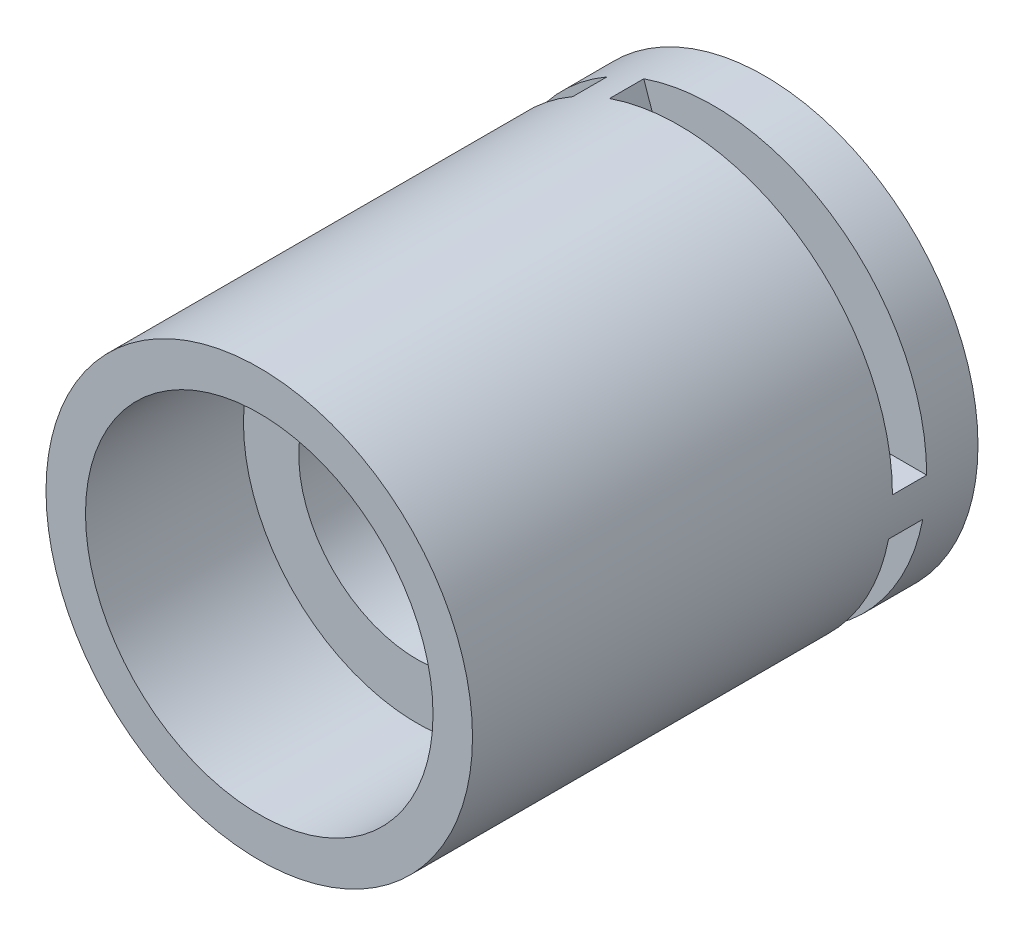
SolidWorks part; units mm, degrees
ref_plane "Front Plane" through (0, 0, 0) normal (0, 0, 1) x (1, 0, 0)
ref_plane "Top Plane" through (0, 0, 0) normal (0, 1, 0) x (1, 0, 0)
ref_plane "Right Plane" through (0, 0, 0) normal (1, 0, 0) x (0, 0, -1)
sketch "Sketch2" plane through (0, 0, 0) normal (0, 0, 1) x (1, 0, 0)
  circle A0 centre (0, 0) radius 13.5
  dimension "D1" = 27
extrude "Boss-Extrude1" add sketch "Sketch2" against normal blind 32
ref_plane "Plane1" through (0, 0, 0) normal (0, 0, 1) x (1, 0, 0)
sketch "Sketch4" plane through (0, 0, 0) normal (0, 0, 1) x (1, 0, 0)
  circle A0 centre (0, 0) radius 11
  dimension "D1" = 22
extrude "Cut-Extrude1" cut sketch "Sketch4" against normal blind 10
sketch "Sketch5" plane through (0, 0, 0) normal (0, 0, 1) x (1, 0, 0)
  circle A0 centre (0, 0) radius 7.5
  dimension "D1" = 15
extrude "Cut-Extrude2" cut sketch "Sketch5" against normal blind 30
sketch "Sketch9" plane through (0, 0, -32) normal (0, 0, -1) x (-1, 0, 0)
  line L0 (0, -18.8285) -> (0, 25.3406) construction
sketch3d "3DSketch4"
  point P0 (4.7437, 12.6391, -18.7172)
ref_plane "Plane5" through (0, 13.5, 0) normal (0, 1, 0) x (1, 0, 0)
sketch "Sketch10" plane through (0, 13.5, 0) normal (0, 1, 0) x (1, 0, 0)
  line L0 (13.5, 32) -> (-13.5, 32) construction
  line L1 (-4.4913, 28.75) -> (21.2187, 28.75)
  line L2 (-4.4913, 28.75) -> (-4.4913, 26.584)
  line L3 (-4.4913, 26.584) -> (21.2187, 26.584)
  line L4 (21.2187, 28.75) -> (21.2187, 26.584)
  dimension "D1" = 25.71
  dimension "D2" = 2.166
  dimension "D3" = 3.25
wrap "Wrap1" sketch "Sketch10" wrap type deboss source sketch "Sketch10" thickness 12 face at (13.5, 0, -32) parameters "D1"=12
pattern_circular "CirPattern1" count 3 over 360 about axis through (0, 0, -32) along (0, 0, 1) of "Wrap1"
